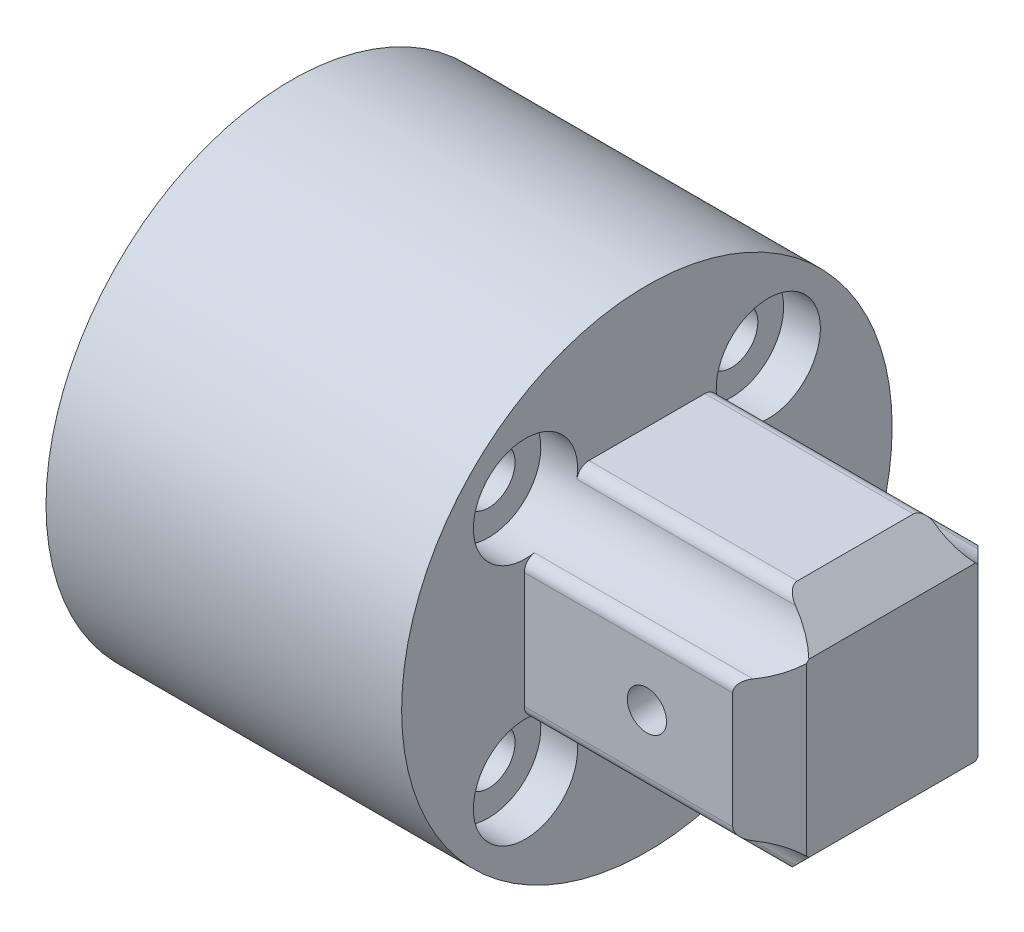
SolidWorks part; units mm, degrees
ref_plane "前视基准面" through (0, 0, 0) normal (0, 0, 1) x (1, 0, 0)
ref_plane "上视基准面" through (0, 0, 0) normal (0, 1, 0) x (1, 0, 0)
ref_plane "右视基准面" through (0, 0, 0) normal (1, 0, 0) x (0, 0, -1)
sketch "草图1" plane through (0, 0, 0) normal (1, 0, 0) x (0, 0, -1)
  circle A0 centre (0, 0) radius 20
  dimension "D1" = 40
extrude "凸台-拉伸1" add sketch "草图1" along normal blind 10
sketch "草图2" plane through (0, 0, 0) normal (-1, 0, 0) x (0, 0, 1)
  line L1 (-7.5, -15.25) -> (7.5, -15.25)
  line L2 (-7.5, -15.25) -> (-7.5, 15.25)
  line L3 (-7.5, 15.25) -> (7.5, 15.25)
  line L4 (7.5, -15.25) -> (7.5, 15.25)
  line L5 (-7.5, -15.25) -> (7.5, 15.25) construction
  line L6 (-7.5, 15.25) -> (7.5, -15.25) construction
  point P0 (0, 0)
  dimension "D1" = 15
  dimension "D2" = 30.5
extrude "切除-拉伸1" cut sketch "草图2" against normal blind 4
sketch "草图3" plane through (4, 0, 0) normal (-1, 0, 0) x (0, 0, 1)
  circle A0 centre (0, 0) radius 8.75
  dimension "D1" = 17.5
extrude "切除-拉伸2" cut sketch "草图3" along normal blind 4
sketch "草图4" plane through (0, 0, 0) normal (-1, 0, 0) x (0, 0, 1)
  line L1 (-9, -16) -> (9, -16)
  line L2 (-9, -16) -> (-9, 16)
  line L3 (-9, 16) -> (9, 16)
  line L4 (9, -16) -> (9, 16)
  line L5 (-9, -16) -> (9, 16) construction
  line L6 (-9, 16) -> (9, -16) construction
  circle A0 centre (0, 0) radius 20
  dimension "D3" = 40
  dimension "D1" = 32
  dimension "D2" = 18
extrude "凸台-拉伸2" add sketch "草图4" along normal blind 19
fillet "圆角1" radius 3 4 edges at (-9.5, -16, -9) (-9.5, -16, 9) (-9.5, 16, -9) (-9.5, 16, 9)
sketch "草图5" plane through (-19, 0, 0) normal (-1, 0, 0) x (0, 0, 1)
  line L0 (-6, -16) -> (6, -16) construction
  line L1 (6, 16) -> (-6, 16) construction
  circle A0 centre (0, -16) radius 2.5
  circle A1 centre (0, 16) radius 2.5
  dimension "D1" = 5
  dimension "D2" = 5
extrude "切除-拉伸3" cut sketch "草图5" against normal blind 20
fillet "圆角2" radius 3 4 edges at (-9.5, -16, -2.5) (-9.5, -16, 2.5) (-9.5, 16, -2.5) (-9.5, 16, 2.5)
sketch "草图6" plane through (10, 0, 0) normal (1, 0, 0) x (0, 0, -1)
  line L0 (0, 0) -> (20, 0) construction
  line L1 (0, 0) -> (18.216, -18.216) construction
  circle A0 centre (0, 0) radius 14 construction
  circle A2 centre (9.8995, -9.8995) radius 2.15
  circle A3 centre (0, 0) radius 14 construction
  circle A4 centre (-9.8995, -9.8995) radius 2.15
  circle A5 centre (0, 0) radius 14 construction
  circle A6 centre (-9.8995, 9.8995) radius 2.15
  circle A7 centre (0, 0) radius 14 construction
  circle A8 centre (9.8995, 9.8995) radius 2.15
  point P21 (0, 0)
  dimension "D1" = 28
  dimension "D3" = 4.3
  dimension "D2" = 45
  dimension "D4" = 4
extrude "切除-拉伸4" cut sketch "草图6" against normal blind 43
fillet "圆角3" radius 1 8 edges at (-9.5, -11.8523, 9) (-9.5, -7.9467, 9) (-9.5, -11.8523, -9) (-9.5, -7.9467, -9) (-9.5, 7.9467, -9) (-9.5, 11.8523, -9) (-9.5, 7.9467, 9) (-9.5, 11.8523, 9)
sketch "草图7" plane through (10, 0, 0) normal (1, 0, 0) x (0, 0, -1)
  circle A0 centre (9.8995, -9.8995) radius 4.25
  dimension "D1" = 8.5
extrude "切除-拉伸5" cut sketch "草图7" against normal blind 3
pattern_circular "阵列(圆周)1" count 4 over 360 about axis through (10, 0, 0) along (1, 0, 0) of "切除-拉伸5"
sketch "草图8" plane through (10, 0, 0) normal (1, 0, 0) x (0, 0, -1)
  line L1 (-10, -10) -> (10, -10)
  line L2 (-10, -10) -> (-10, 10)
  line L3 (-10, 10) -> (10, 10)
  line L4 (10, -10) -> (10, 10)
  line L5 (-10, -10) -> (10, 10) construction
  line L6 (-10, 10) -> (10, -10) construction
  point P0 (0, 0)
  dimension "D1" = 20
  dimension "D2" = 20
extrude "凸台-拉伸3" add sketch "草图8" along normal blind 20
sketch "草图9" plane through (0, 0, -10) normal (0, 0, -1) x (-1, 0, 0)
  line L0 (-10, 20) -> (-10, -20) construction
  circle A0 centre (-20, 0) radius 1.6
  dimension "D1" = 3.2
  dimension "D2" = 10
extrude "切除-拉伸6" cut sketch "草图9" against normal blind 27
chamfer "倒角1" distance 3 angle 45 4 edges at (30, -10, 0) (30, 0, 10) (30, 10, 0) (30, 0, -10)
sketch "草图11" plane through (10, 0, 0) normal (1, 0, 0) x (0, 0, -1)
  circle A0 centre (-9.8995, 9.8995) radius 4.25
  circle A1 centre (-9.8995, -9.8995) radius 4.25
  circle A2 centre (9.8995, -9.8995) radius 4.25
  circle A3 centre (9.8995, 9.8995) radius 4.25
  point P12 (0, 0)
  dimension "D1" = 8.5
  dimension "D2" = 4
extrude "切除-拉伸7" cut sketch "草图11" along normal blind 49
sketch "草图12" plane through (0, -15.25, 0) normal (0, 1, 0) x (1, 0, 0)
  line L1 (1.5, -2.5) -> (-1.5, -2.5)
  line L2 (1.5, -2.5) -> (1.5, 2.5)
  line L3 (1.5, 2.5) -> (-1.5, 2.5)
  line L4 (-1.5, -2.5) -> (-1.5, 2.5)
  line L5 (1.5, -2.5) -> (-1.5, 2.5) construction
  line L6 (1.5, 2.5) -> (-1.5, -2.5) construction
  point P0 (0, 0)
  dimension "D1" = 3
  dimension "D2" = 5
extrude "切除-拉伸8" cut sketch "草图12" against normal blind 49
fillet "圆角4" radius 1 3 edges at (0.75, -15.25, 2.5) (0.75, -15.25, -2.5) (1.5, -15.25, 0)
fillet "圆角5" radius 1 4 edges at (0, -19.8431, 2.5) (1.5, -20, 0) (0, -19.8431, -2.5) (-1.5, -20, 0)
fillet "圆角6" radius 1 7 edges at (18.5, 5.6507, -10) (18.5, 10, -5.6507) (18.5, 10, 5.6507) (18.5, 5.6507, 10) (18.5, -5.6507, 10) (18.5, -10, 5.6507) (18.5, -10, -5.6507)
fillet "圆角7" radius 1 1 edges at (18.5, -5.6507, -10)
